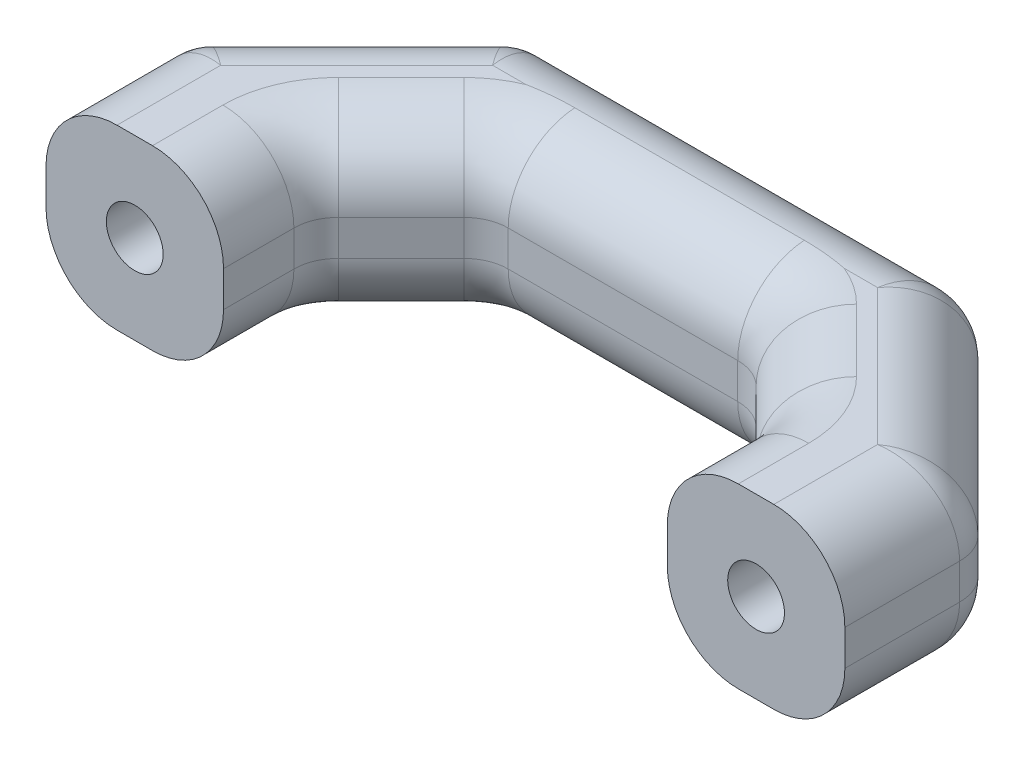
SolidWorks part; units mm, degrees
ref_plane "Front Plane" through (0, 0, 0) normal (0, 0, 1) x (1, 0, 0)
ref_plane "Top Plane" through (0, 0, 0) normal (0, 1, 0) x (1, 0, 0)
ref_plane "Right Plane" through (0, 0, 0) normal (1, 0, 0) x (0, 0, -1)
sketch "Sketch2" plane through (0, 0, 0) normal (0, 1, 0) x (1, 0, 0)
  line L0 (-25, 0) -> (-25, 20)
  line L1 (-55, 0) -> (55, 0) construction
  line L2 (-25, 20) -> (25, 20)
  line L3 (0, -55) -> (0, 55) construction
  line L4 (-25, 0) -> (-45, 0)
  line L5 (-45, 0) -> (-45, 35)
  line L6 (-45, 35) -> (45, 35)
  line L7 (45, 0) -> (45, 35)
  line L8 (25, 0) -> (45, 0)
  line L9 (25, 0) -> (25, 20)
  point P12 (0, 35)
  point P15 (0, 20)
  dimension "D1" = 25
  dimension "D2" = 35
  dimension "D3" = 20
  dimension "D4" = 20
extrude "Boss-Extrude1" add sketch "Sketch2" along normal blind 20
chamfer "Chamfer1" distance 10 angle 45 2 edges at (25, 10, -20) (-25, 10, -20)
chamfer "Chamfer2" distance 20 angle 45 2 edges at (-45, 10, -35) (45, 10, -35)
fillet "Fillet2" radius 5 8 edges at (-25, 10, -35) (-45, 10, -15) (45, 10, -15) (25, 10, -35) (-25, 10, -10) (-15, 10, -20) (25, 10, -10) (15, 10, -20)
fillet "Fillet3" radius 8 36 edges at (45, 0, -6.4645) (44.6194, 0, -14.8423) (35, 0, -25) (24.8423, 0, -34.6194) (-45, 0, -6.4645) (-44.6194, 0, -14.8423) (-35, 0, -25) (-24.8423, 0, -34.6194) (0, 0, -35) (45, 20, -6.4645) (44.6194, 20, -14.8423) (35, 20, -25) (24.8423, 20, -34.6194) (-45, 20, -6.4645) (-44.6194, 20, -14.8423) (-35, 20, -25) (-24.8423, 20, -34.6194) (0, 20, -35) (-25, 20, -3.9645) (-24.6194, 20, -9.8423) (-20, 20, -15) (-14.8423, 20, -19.6194) (25, 20, -3.9645) (24.6194, 20, -9.8423) (20, 20, -15) (14.8423, 20, -19.6194) (-25, 0, -3.9645) (-24.6194, 0, -9.8423) (-20, 0, -15) (-14.8423, 0, -19.6194) (25, 0, -3.9645) (24.6194, 0, -9.8423) (20, 0, -15) (14.8423, 0, -19.6194) (0, 20, -20) (0, 0, -20)
sketch "Sketch3" plane through (0, 0, 0) normal (0, 0, 1) x (1, 0, 0)
  line L0 (55, 0) -> (-55, 0) construction
  line L1 (0, -55) -> (0, 55) construction
  circle A0 centre (-35, 10) radius 3.2
  circle A1 centre (35, 10) radius 3.2
  dimension "D1" = 10
  dimension "D2" = 35
extrude "Cut-Extrude1" cut sketch "Sketch3" against normal blind 12
